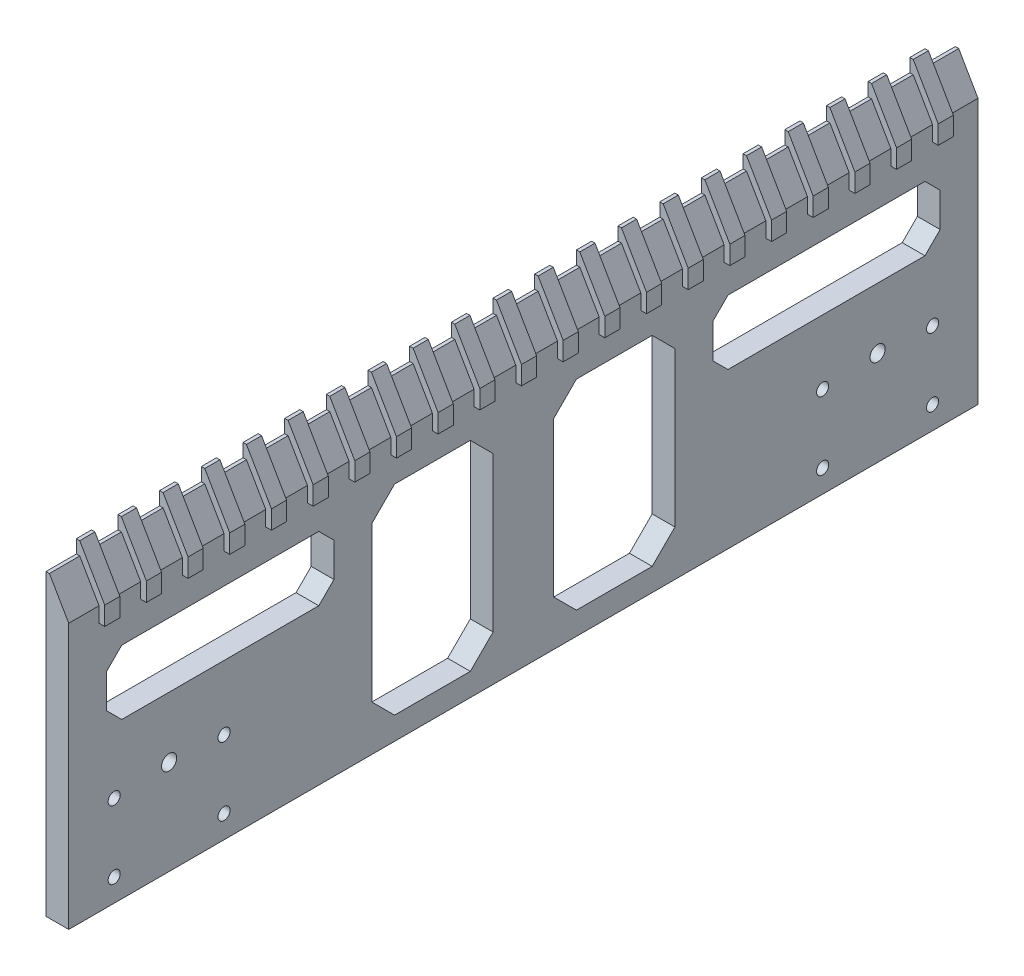
SolidWorks part; units mm, degrees
ref_plane "前视基准面" through (0, 0, 0) normal (0, 0, 1) x (1, 0, 0)
ref_plane "上视基准面" through (0, 0, 0) normal (0, 1, 0) x (1, 0, 0)
ref_plane "右视基准面" through (0, 0, 0) normal (1, 0, 0) x (0, 0, -1)
sketch "草图1" plane through (0, 0, 0) normal (1, 0, 0) x (0, 0, -1)
  line L1 (0, 0) -> (240, 0)
  line L2 (0, 0) -> (0, -70)
  line L3 (0, -70) -> (240, -70)
  line L4 (240, 0) -> (240, -70)
  dimension "D1" = 240
  dimension "D2" = 70
extrude "凸台-拉伸1" add sketch "草图1" along normal blind 6
sketch "草图3" plane through (6, 0, 0) normal (1, 0, 0) x (0, 0, -1)
  line L0 (120, 0) -> (120, -70) construction
  line L1 (14, -12) -> (66, -12)
  line L2 (10, -16) -> (10, -25)
  line L3 (14, -29) -> (66, -29)
  line L4 (70, -16) -> (70, -25)
  line L5 (240, 0) -> (0, 0) construction
  line L6 (0, -70) -> (240, -70) construction
  line L7 (0, 0) -> (0, -70) construction
  line L12 (10, -16) -> (14, -12)
  line L13 (10, -25) -> (14, -29)
  line L14 (66, -29) -> (70, -25)
  line L15 (66, -12) -> (70, -16)
  line L28 (80, -17.2) -> (86, -11.2)
  line L42 (86, -11.2) -> (106, -11.2)
  line L43 (80, -17.2) -> (80, -58)
  line L44 (86, -64) -> (106, -64)
  line L45 (112, -17.2) -> (112, -58)
  line L46 (106, -11.2) -> (112, -17.2)
  line L47 (106, -64) -> (112, -58)
  line L48 (80, -58) -> (86, -64)
  point P0 (10, -12)
  point P1 (70, -29)
  point P2 (10, -29)
  point P3 (70, -12)
  point P20 (80, -11.2)
  point P21 (112, -64)
  point P22 (80, -64)
  point P23 (112, -11.2)
  dimension "D1" = 10
  dimension "D2" = 12
  dimension "D3" = 17
  dimension "D4" = 60
  dimension "D5" = 11.2
  dimension "D6" = 6
  dimension "D7" = 52.8
  dimension "D12" = 80
  dimension "D13" = 8
  dimension "D14" = 32
extrude "切除-拉伸2" cut sketch "草图3" against normal through all
sketch "草图2" plane through (0, 0, 0) normal (1, 0, 0) x (0, 0, -1)
  line L0 (0, 0) -> (0, -70) construction
  line L1 (12, -46) -> (41, -46) construction
  line L2 (12, -46) -> (12, -64) construction
  line L3 (12, -64) -> (41, -64) construction
  line L4 (41, -46) -> (41, -64) construction
  line L5 (240, 0) -> (0, 0) construction
  line L6 (120, 0) -> (120, -70) construction
  circle A0 centre (12, -46) radius 1.55
  circle A1 centre (41, -64) radius 1.55
  circle A2 centre (41, -46) radius 1.55
  circle A3 centre (12, -64) radius 1.55
  dimension "D5" = 3.1
  dimension "D1" = 12
  dimension "D2" = 46
  dimension "D3" = 29
  dimension "D4" = 18
sketch "草图6" plane through (0, 0, 0) normal (0, 0, 1) x (1, 0, 0)
  line L0 (6, 0) -> (0, 0)
  line L1 (0, 0) -> (0, 8.8335)
  line L2 (0.9, 8.8335) -> (6, 0)
  line L3 (0, 8.8335) -> (0.9, 8.8335)
  line L4 (0, 8.8335) -> (0, 10.3923) construction
  line L5 (0, 10.3923) -> (0.9, 8.8335) construction
  dimension "D1" = 30
  dimension "D2" = 0.9
extrude "凸台-拉伸2" add sketch "草图6" against normal blind 240
ref_plane "基准面1" through (0, 0, -120) normal (0, 0, 1) x (1, 0, 0)
sketch "草图8" plane through (0, 0, -120) normal (0, 0, 1) x (1, 0, 0)
  line L0 (0, 10.3923) -> (0, 12.3335)
  line L1 (0.9, 12.3335) -> (7.5, 0.9019)
  line L2 (7.5, 0.9019) -> (7.5, -4)
  line L3 (7.5, -4) -> (6, -4)
  line L4 (6, 0) -> (6, -70) construction
  line L5 (6, -4) -> (6, 0)
  line L6 (6, 0) -> (0.9, 8.8335) construction
  line L7 (6, 0) -> (0.9, 8.8335)
  line L8 (0, 12.3335) -> (0.9, 12.3335)
  line L9 (0, 12.3335) -> (0, 13.8923) construction
  line L10 (0, 13.8923) -> (0.9, 12.3335) construction
  line L11 (0, 10.3923) -> (0, 8.8335)
  line L12 (0, 8.8335) -> (0.9, 8.8335)
  line L13 (0.9, 8.8335) -> (0, 10.3923) construction
  dimension "D1" = 3.5
  dimension "D2" = 1.5
  dimension "D3" = 4
  dimension "D4" = 0.9
extrude "凸台-拉伸3" add sketch "草图8" along normal mid plane 4
pattern_linear "阵列(线性)1" count 11 spacing 11 along (0, 0, 1) count 11 spacing 11 along (0, 0, -1) of "凸台-拉伸3"
hole_wizard "打孔尺寸(%根据)内六角圆柱头螺钉的类型1" positions "草图14" profile "草图15" counterbore size "M3" standard "GB" end condition through all
sketch "草图14" plane through (0, 0, 0) normal (-1, 0, 0) x (0, 0, 1)
  point P0 (-41, -46)
  point P3 (-12, -46)
  point P6 (-12, -64)
  point P9 (-41, -64)
sketch "草图15" plane through (0, -46, -41) normal (0, 1, 0) x (0, 0, 1)
  line L0 (0, 0) -> (0, 7.5)
  line L1 (0, 7.5) -> (1.6, 7.5)
  line L3 (1.6, 7.5) -> (1.6, 3.4)
  line L4 (1.6, 3.4) -> (3, 3.4)
  line L5 (3, 3.4) -> (3, 0)
  line L7 (3, 0) -> (0, 0)
  line L11 (0, -6.35) -> (0, 107.95) construction
  dimension "通孔孔直径" = 3.2
  dimension "通孔孔深度" = 7.5
  dimension "柱形沉头孔直径" = 6
  dimension "柱形沉头孔深度" = 3.4
sketch "草图16" plane through (0, 0, 0) normal (-1, 0, 0) x (0, 0, 1)
  line L0 (-12, -46) -> (-41, -46) construction
  line L1 (-26.5, -46) -> (-26.5, -29) construction
  line L2 (-14, -29) -> (-66, -29) construction
  line L3 (-26.5, -46) -> (-26.5, -70) construction
  line L4 (0, -70) -> (-240, -70) construction
  circle A0 centre (-26.5, -45.0233) radius 2
  dimension "D1" = 4
extrude "切除-拉伸3" cut sketch "草图16" against normal blind 10
mirror "镜向1" about plane through (0, 0, -120) normal (0, 0, 1) of "打孔尺寸(%根据)内六角圆柱头螺钉的类型1"
mirror "镜向2" about plane through (0, 0, -120) normal (0, 0, 1) of "切除-拉伸3", "切除-拉伸2"
